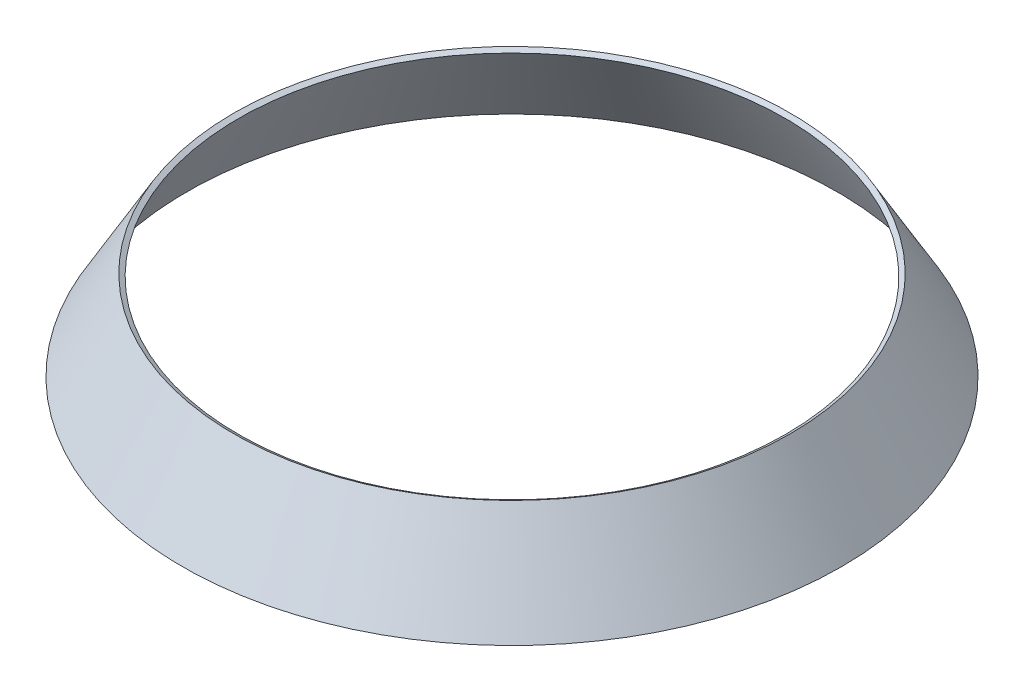
SolidWorks part; units mm, degrees
ref_plane "Front Plane" through (0, 0, 0) normal (0, 0, 1) x (1, 0, 0)
ref_plane "Top Plane" through (0, 0, 0) normal (0, 1, 0) x (1, 0, 0)
ref_plane "Right Plane" through (0, 0, 0) normal (1, 0, 0) x (0, 0, -1)
sketch "Sketch1" plane through (0, 0, 0) normal (0, 0, 1) x (1, 0, 0)
  line L0 (0, -1106.9178) -> (0, 54238.9737) construction
  line L1 (37.78, 6.2372) -> (44.78, -5.8872)
  line L2 (37.78, 6.2372) -> (37.1738, 5.8872)
  line L3 (44.78, -5.8872) -> (44.1738, -6.2372)
  line L4 (37.1738, 5.8872) -> (44.1738, -6.2372)
  line L5 (37.78, 6.2372) -> (44.1738, -6.2372) construction
  line L6 (44.78, -5.8872) -> (37.1738, 5.8872) construction
  point P4 (40.9769, 0)
  dimension "D1" = 30
  dimension "D2" = 0.7
  dimension "D3" = 44.78
  dimension "D4" = 14
revolve "Revolve1" add sketch "Sketch1" angle 360 about L0
